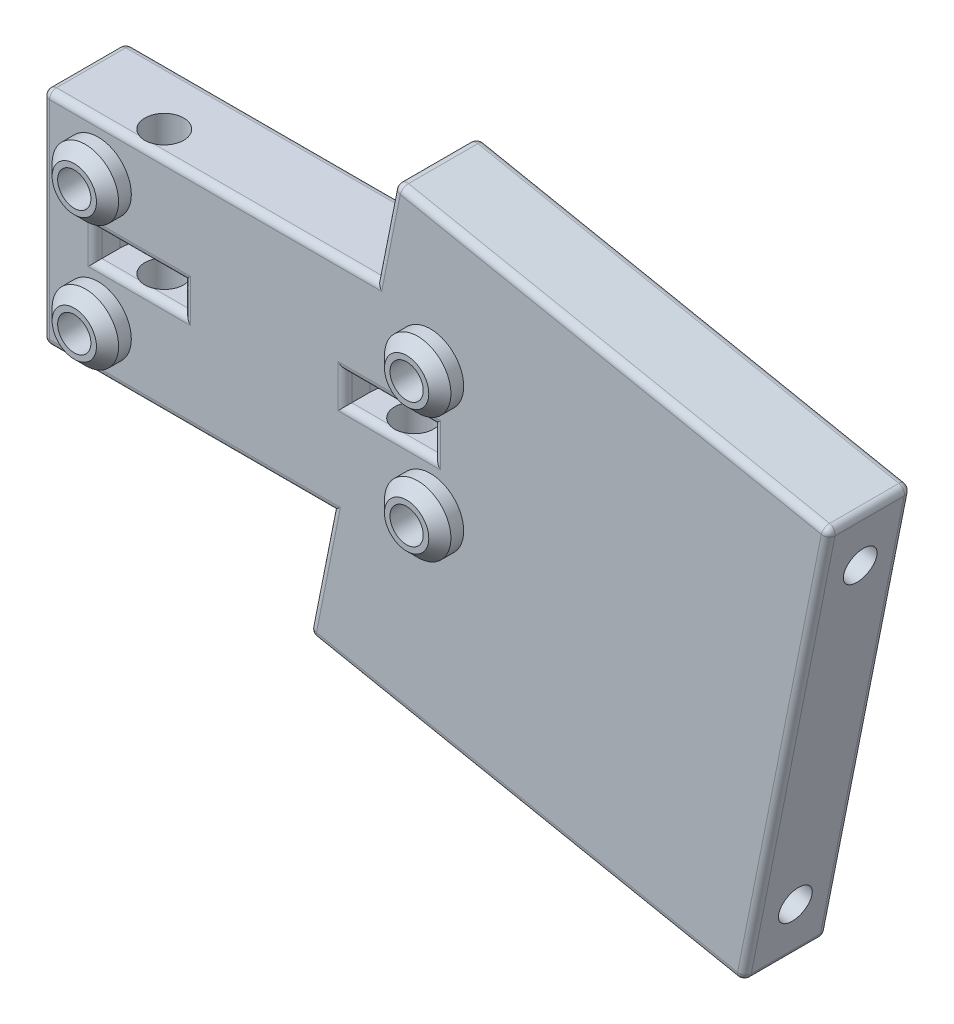
SolidWorks part; units mm, degrees
ref_plane "Front Plane" through (0, 0, 0) normal (0, 0, 1) x (1, 0, 0)
ref_plane "Top Plane" through (0, 0, 0) normal (0, 1, 0) x (1, 0, 0)
ref_plane "Right Plane" through (0, 0, 0) normal (1, 0, 0) x (0, 0, -1)
sketch "Sketch1" plane through (0, 0, 0) normal (0, 0, 1) x (1, 0, 0)
  line L2 (-38.1, -12.7) -> (-38.1, 12.7)
  line L3 (-38.1, 12.7) -> (38.1, 12.7)
  line L10 (38.1, -12.7) -> (38.1, 12.7)
  line L11 (-38.1, -12.7) -> (38.1, -12.7)
  line L14 (-38.1, 12.7) -> (38.1, -12.7) construction
  point P2 (0, 0)
  dimension "D1" = 76.2
  dimension "D2" = 25.4
extrude "Boss-Extrude1" add sketch "Sketch1" along normal blind 9.525
sketch "Sketch6" plane through (0, 0, 9.525) normal (0, 0, -1) x (-1, 0, 0)
  line L4 (7.6422, -26.3067) -> (-42.1817, -36.2172)
  line L6 (7.6422, -26.3067) -> (-2.2683, 23.5172)
  line L23 (-42.1817, -36.2172) -> (-52.0922, 13.6067)
  line L24 (-2.2683, 23.5172) -> (-52.0922, 13.6067)
  line L25 (7.6422, -26.3067) -> (-52.0922, 13.6067) construction
  line L26 (-42.1817, -36.2172) -> (-2.2683, 23.5172) construction
  line L27 (-38.1, 12.7) -> (38.1, 12.7) construction
  point P1 (-22.225, -6.35)
  dimension "D1" = 50.8
  dimension "D2" = 50.8
  dimension "D3" = 11.25
  dimension "D4" = 6.35
  dimension "D5" = 22.225
extrude "Boss-Extrude2" add sketch "Sketch6" along normal up to surface (9.525 mm away) up to face at (0, 0, 0)
sketch "Sketch4" plane through (0, 0, 0) normal (0, 1, 0) x (1, 0, 0)
  line L7 (0.1167, -9.525) -> (-38.1, -9.525) construction
  line L8 (-32.0992, -6.6675) -> (-32.0992, -9.525)
  line L9 (-21.9392, -6.6675) -> (-21.9392, -9.525)
  line L10 (-21.9392, -9.525) -> (-32.0992, -9.525)
  line L11 (-38.1, -9.525) -> (-38.1, 0) construction
  arc A2 (-21.9392, -6.6675) -> (-32.0992, -6.6675) centre (-27.0192, -6.6675) ccw
  dimension "D1" = 10.16
  dimension "D2" = 2.8575
  dimension "D3" = 11.0808
extrude "Cut-Extrude2" cut sketch "Sketch4" against normal mid plane 3.302
ref_plane "Plane3" through (-12.7, 0, 0) normal (-1, 0, 0) x (0, 0, 1)
sketch "Sketch2" plane through (0, 0, 9.525) normal (0, 0, 1) x (1, 0, 0)
  line L1 (-38.1, 12.7) -> (-38.1, -12.7) construction
  line L2 (0, 0) -> (-38.1, 0) construction
  line L3 (-38.1, 12.7) -> (-38.1, -12.7) construction
  circle A0 centre (-31.75, 7.1755) radius 1.905
  circle A1 centre (-31.75, -7.1755) radius 1.905
  dimension "D1" = 3.81
  dimension "D2" = 14.351
  dimension "D3" = 6.35
extrude "Cut-Extrude1" cut sketch "Sketch2" against normal through all both and the other way through all
sketch "Sketch11" plane through (0, 0, 9.525) normal (0, 0, 1) x (1, 0, 0)
  circle A0 centre (-31.75, 7.1755) radius 3.81
  circle A1 centre (-31.75, 7.1755) radius 1.905
  circle A2 centre (-31.75, 7.1755) radius 1.905 construction
  circle A3 centre (-31.75, -7.1755) radius 3.81
  circle A4 centre (-31.75, -7.1755) radius 1.905
  dimension "D1" = 7.62
extrude "Boss-Extrude5" add sketch "Sketch11" along normal blind 2.7305
sketch "Sketch5" plane through (0, 12.7, 0) normal (0, 1, 0) x (1, 0, 0)
  line L0 (0.1167, -9.525) -> (-38.1, -9.525) construction
  line L1 (-38.1, -9.525) -> (-38.1, 0) construction
  circle A0 centre (-27.0192, -6.6675) radius 2.2225
  dimension "D3" = 4.445
  dimension "D1" = 2.8575
  dimension "D2" = 11.0808
extrude "Cut-Extrude3" cut sketch "Sketch5" against normal through all
mirror "Mirror1" about plane through (-12.7, 0, 0) normal (-1, 0, 0) of "Boss-Extrude5", "Cut-Extrude2", "Cut-Extrude3", "Cut-Extrude1"
chamfer "Chamfer4" distance 1.27 angle 45 4 edges at (-27.94, -7.1755, 12.2555) (2.54, -7.1755, 12.2555) (2.54, 7.1755, 12.2555) (-27.94, 7.1755, 12.2555)
fillet "Fillet3" radius 0.7937 30 edges at (-38.1, 0, 9.525) (-38.1, -12.7, 4.7625) (-38.1, 0, 0) (-38.1, 12.7, 4.7625) (-18.9917, 12.7, 0) (-18.9917, 12.7, 9.525) (1.1925, 18.1086, 9.525) (1.1925, 18.1086, 0) (2.2683, 23.5172, 4.7625) (27.1803, 18.5619, 0) (27.1803, 18.5619, 9.525) (52.0922, 13.6067, 4.7625) (47.1369, -11.3053, 0) (47.1369, -11.3053, 9.525) (42.1817, -36.2172, 4.7625) (17.2697, -31.2619, 0) (17.2697, -31.2619, 9.525) (-7.6422, -26.3067, 4.7625) (-6.289, -19.5033, 9.525) (-6.289, -19.5033, 0) (-21.5179, -12.7, 0) (-21.5179, -12.7, 9.525) (1.6193, -1.651, 9.525) (6.6993, 0, 9.525) (1.6193, 1.651, 9.525) (-3.4607, 0, 9.525) (-21.9392, 0, 9.525) (-32.0992, 0, 9.525) (-27.0192, 1.651, 9.525) (-27.0192, -1.651, 9.525)
sketch "Sketch12" plane through (47.5061, -9.4495, 0) normal (0.9808, -0.1951, 0) x (0, 0, -1)
  circle A6 centre (-4.7625, -20.9421) radius 1.905
  circle A7 centre (-4.7625, 17.1579) radius 1.905
  dimension "D1" = 3.81
extrude "Cut-Extrude4" cut sketch "Sketch12" against normal blind 9.525
sketch "Sketch13" plane through (-2.3178, 0.461, 0) normal (-0.9808, 0.1951, 0) x (0, 0, 1)
  circle A0 centre (4.7625, 17.1579) radius 1.905
  circle A1 centre (4.7625, -20.9421) radius 1.905
  dimension "D1" = 3.81
extrude "Cut-Extrude5" cut sketch "Sketch13" against normal blind 9.525
